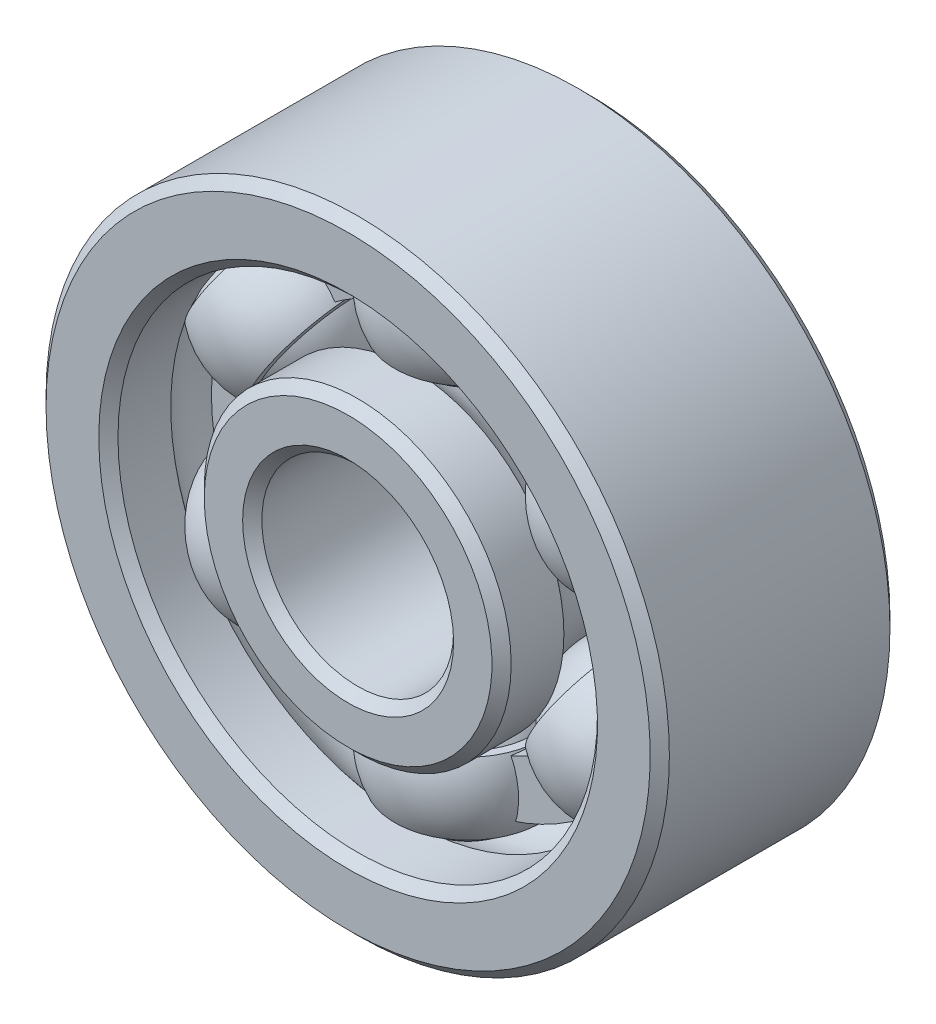
SolidWorks part; units mm, degrees
material "Alloy Steel"
ref_plane "Front" through (0, 0, 0) normal (0, 0, 1) x (1, 0, 0)
ref_plane "Top" through (0, 0, 0) normal (0, 1, 0) x (1, 0, 0)
ref_plane "Right" through (0, 0, 0) normal (1, 0, 0) x (0, 0, -1)
ref_axis "Ось1" through (0, 0, -80.9) along (0, 0, 1)
sketch "Sketch1" plane through (0, 0, 0) normal (1, 0, 0) x (0, 0, -1)
  line L0 (0, 6.5) -> (0, 0) construction
  line L1 (-2.5, 6.5) -> (2.5, 6.5)
  line L2 (-2.5, 6.5) -> (-2.5, 5)
  line L3 (-2.5, 5) -> (-1.2, 5)
  line L4 (2.5, 6.5) -> (2.5, 5)
  line L5 (-2.5, 3.2) -> (-1.2, 3.2)
  line L6 (-2.5, 3.2) -> (-2.5, 2)
  line L7 (-2.5, 2) -> (2.5, 2)
  line L8 (2.5, 3.2) -> (2.5, 2)
  line L9 (-2.5, 5) -> (2.5, 3.2) construction
  line L10 (2.5, 5) -> (-2.5, 3.2) construction
  line L11 (1.2, 5) -> (2.5, 5)
  line L12 (1.2, 3.2) -> (2.5, 3.2)
  line L13 (0, 0) -> (2.5, 0) construction
  arc A0 (1.2, 5) -> (-1.2, 5) centre (0, 4.1) ccw
  arc A1 (-1.2, 3.2) -> (1.2, 3.2) centre (0, 4.1) ccw
  dimension "D7" = 1.5
  dimension "D1" = 1.2
  dimension "D2" = 1.5
  dimension "D3" = 2
  dimension "D4" = 6.5
  dimension "D5" = 5
  dimension "D6" = 1.8
sketch "Sketch2" plane through (0, 0, 0) normal (1, 0, 0) x (0, 0, -1)
  line L0 (0, 2.5873) -> (0, 5.6127)
  arc A0 (0, 2.6) -> (0, 5.6) centre (0, 4.1) ccw construction
  arc A1 (1.2, 5) -> (-1.2, 5) centre (0, 4.1) ccw construction
  arc A2 (0, 2.5873) -> (0, 5.6127) centre (0, 4.1) ccw
  dimension "D1" = 0.0127
sketch "Sketch3" plane through (0, 0, 0) normal (1, 0, 0) x (0, 0, -1)
  line L4 (1.3565, 3.35) -> (1.5256, 3.35)
  line L6 (1.2, 3.2) -> (2.5, 3.2) construction
  line L7 (1.3565, 4.85) -> (1.5256, 4.85)
  line L8 (1.2, 5) -> (2.5, 5) construction
  arc A0 (1.5256, 3.35) -> (1.5256, 4.85) centre (0, 4.1) ccw
  arc A2 (1.2, 5) -> (-1.2, 5) centre (0, 4.1) ccw construction
  arc A3 (1.3565, 3.35) -> (1.3565, 4.85) centre (0, 4.1) ccw
  dimension "D2" = 0.05
  dimension "D4" = 0.15
  dimension "D5" = 0.15
revolve "Revolve1" add sketch "Sketch1" angle 360 about L13
revolve "Revolve2" add sketch "Sketch2" angle 360 about L0
pattern_circular "CirPattern1" count 6 over 360 about axis through (0, 0, 0) along (0, 0, 1) of bodies 104
revolve "Revolve3" add sketch "Sketch3" angle 360 about L0
pattern_circular "CirPattern2" count 6 over 360 about axis through (0, 0, 0) along (0, 0, 1) of bodies 112
sketch "Sketch5" plane through (0, 0, 0) normal (0, 0, 1) x (1, 0, 0)
  circle A0 centre (0, 0) radius 3.2 construction
  circle A2 centre (0, 0) radius 3.2 construction
  circle A3 centre (0, 0) radius 5 construction
  arc A4 (-1.4343, 4.5807) -> (-3.2499, 3.5325) centre (0, 0) ccw
  arc A5 (-1.3613, 3.4405) -> (-2.2988, 2.8992) centre (0, 0) ccw
  circle A6 centre (-3.5507, 2.05) radius 1.5127 construction
  circle A7 centre (0, 4.1) radius 1.5127 construction
  arc A8 (-2.2988, 2.8992) -> (-3.2499, 3.5325) centre (-3.5507, 2.05) ccw
  arc A9 (-1.4343, 4.5807) -> (-1.3613, 3.4405) centre (0, 4.1) ccw
  circle A10 centre (0, 0) radius 4.8 construction
  circle A11 centre (0, 0) radius 3.7 construction
  circle A13 centre (0, 0) radius 5 construction
  dimension "D1" = 0.2
  dimension "D2" = 0.5
extrude "Extrude1" add sketch "Sketch5" along normal mid plane 1.1 separate body
pattern_circular "CirPattern4" count 6 over 360 about axis through (0, 0, 0) along (0, 0, -1) reverse direction yes of bodies 154
chamfer "Chamfer1" distance 0.2 angle 45 4 edges at (2, 0, -2.5) (3.2, 0, -2.5) (3.2, 0, 2.5) (2, 0, 2.5)
chamfer "Фаска1" distance 0.2 angle 45 4 edges at (6.5, 0, 2.5) (5, 0, 2.5) (5, 0, -2.5) (6.5, 0, -2.5)
